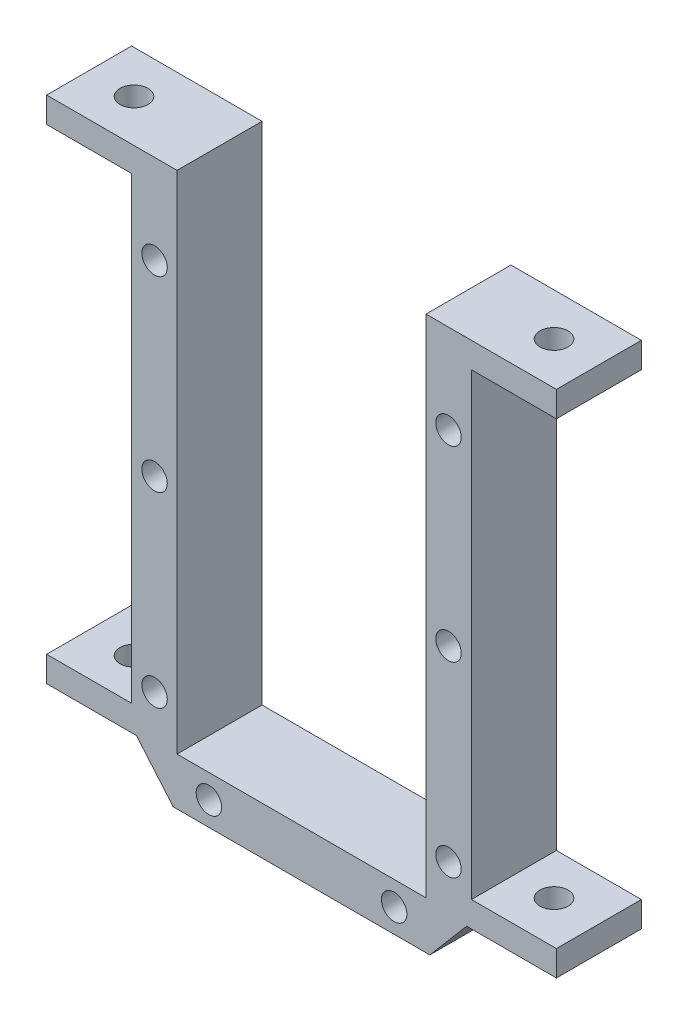
SolidWorks part; units mm, degrees
material "AISI 1035 Acier (SS)"
ref_plane "Front Plane" through (0, 0, 0) normal (0, 0, 1) x (1, 0, 0)
ref_plane "Top Plane" through (0, 0, 0) normal (0, 1, 0) x (1, 0, 0)
ref_plane "Right Plane" through (0, 0, 0) normal (1, 0, 0) x (0, 0, -1)
sketch "Sketch1" plane through (0, 0, 0) normal (0, 0, 1) x (1, 0, 0)
  line L1 (-20.1, 32.55) -> (19.9, 32.55)
  line L2 (-20.1, 32.55) -> (-20.1, -32.55)
  line L3 (-20.1, -32.55) -> (19.9, -32.55)
  line L4 (19.9, 32.55) -> (19.9, -32.55)
  point P0 (0, 0)
  dimension "D1" = 40
  dimension "D2" = 65.1
extrude "Boss-Extrude1" add sketch "Sketch1" along normal blind 10
sketch "Sketch2" plane through (0, 0, 10) normal (0, 0, 1) x (1, 0, 0)
  line L0 (-0.1, 32.55) -> (-0.1, -32.55) construction
  line L1 (19.9, 32.55) -> (-20.1, 32.55) construction
  line L2 (-20.1, -32.55) -> (19.9, -32.55) construction
  line L3 (-20.1, 0) -> (19.9, 0) construction
  line L4 (-20.1, 32.55) -> (-20.1, -32.55) construction
  line L5 (19.9, -32.55) -> (19.9, 32.55) construction
  line L6 (-20.1, -27.45) -> (19.9, -27.45) construction
  line L7 (15, -32.55) -> (19.335, -27.45)
  line L8 (19.335, -27.45) -> (15, -32.55) construction
  line L9 (19.335, -27.45) -> (19.9, -27.45)
  line L22 (19.9, -27.45) -> (19.9, -32.55)
  line L23 (19.9, -32.55) -> (15, -32.55)
  line L24 (-20.1, -27.45) -> (-20.1, -32.55)
  line L25 (-19.535, -27.45) -> (-20.1, -27.45)
  line L26 (-15.2, -32.55) -> (-19.535, -27.45)
  line L27 (-20.1, -32.55) -> (-15.2, -32.55)
  point P12 (-0.1, -27.45)
  point P13 (-19.535, -27.45)
  point P17 (-0.1, -27.45)
  point P18 (19.335, -27.45)
  dimension "D1" = 60
extrude "Cut-Extrude1" cut sketch "Sketch2" against normal blind 10
sketch "Sketch4" plane through (0, 0, 10) normal (0, 0, 1) x (1, 0, 0)
  line L0 (-0.1, 32.55) -> (-0.1, -32.55) construction
  line L1 (19.9, 32.55) -> (-20.1, 32.55) construction
  line L2 (-15.2, -32.55) -> (15, -32.55) construction
  line L3 (-20.1, 2.55) -> (19.9, 2.55) construction
  line L4 (-20.1, 32.55) -> (-20.1, -27.45) construction
  line L5 (19.9, -27.45) -> (19.9, 32.55) construction
  line L6 (14.55, -26.95) -> (-14.75, -26.95) construction
  line L7 (-14.75, -26.95) -> (-14.75, 32.55) construction
  line L8 (14.55, -26.95) -> (14.55, 32.55) construction
  line L9 (-14.75, 32.55) -> (-14.75, -26.95)
  line L10 (-14.75, -26.95) -> (14.55, -26.95)
  line L11 (14.55, -26.95) -> (14.55, 32.55)
  line L12 (14.55, 32.55) -> (-14.75, 32.55)
  point P12 (-0.1, -26.95)
  point P16 (-0.1, -26.95)
  dimension "D1" = 5.6
  dimension "D2" = 29.3
extrude "Cut-Extrude2" cut sketch "Sketch4" against normal blind 10
sketch "Sketch5" plane through (0, 0, 10) normal (0, 0, 1) x (1, 0, 0)
  line L0 (-14.75, 32.55) -> (14.55, 32.55) construction
  line L1 (-0.1, 32.55) -> (-0.1, -32.55) construction
  line L2 (-15.2, -32.55) -> (15, -32.55) construction
  line L3 (-15.2, -32.55) -> (15, -32.55) construction
  line L6 (-20.1, 32.55) -> (-20.1, -27.45) construction
  circle A0 centre (-17.4, 22.05) radius 1.5
  circle A1 centre (-17.4, 0.05) radius 1.5
  circle A2 centre (-17.4, -21.95) radius 1.5
  circle A3 centre (-11, -29.75) radius 1.5
  circle A4 centre (10.8, -29.75) radius 1.5
  circle A5 centre (17.2, -21.95) radius 1.5
  circle A6 centre (17.2, 0.05) radius 1.5
  circle A7 centre (17.2, 22.05) radius 1.5
  point P8 (-17.4, 22.05)
  point P9 (-17.4, 0.05)
  point P10 (-17.4, -21.95)
  point P11 (-11, -29.75)
  point P22 (10.8, -29.75)
  point P25 (17.2, -21.95)
  point P28 (17.2, 0.05)
  point P31 (17.2, 22.05)
  dimension "D6" = 3
  dimension "D7" = 3
  dimension "D8" = 3
  dimension "D9" = 3
  dimension "D1" = 10.6
  dimension "D2" = 32.6
  dimension "D3" = 54.6
  dimension "D4" = 2.8
  dimension "D5" = 9.1
  dimension "D10" = 17.3
  dimension "D11" = 17.3
  dimension "D12" = 17.3
extrude "Cut-Extrude3" cut sketch "Sketch5" against normal blind 10
sketch "Sketch6" plane through (0, 0, 10) normal (0, 0, 1) x (1, 0, 0)
  line L0 (-14.75, 32.55) -> (14.55, 32.55) construction
  line L1 (-0.1, 32.55) -> (-0.1, -32.55) construction
  line L2 (-15.2, -32.55) -> (15, -32.55) construction
  line L3 (-20.1, 2.55) -> (19.9, 2.55) construction
  line L4 (-20.1, 32.55) -> (-20.1, -27.45) construction
  line L5 (19.9, -27.45) -> (19.9, 32.55) construction
sketch "Sketch7" plane through (19.9, 0, 0) normal (1, 0, 0) x (0, 0, -1)
  line L0 (0, 2.55) -> (-10, 2.55) construction
  line L1 (-10, 32.55) -> (-10, -32.55) construction
  line L2 (0, -27.45) -> (0, 32.55) construction
  line L3 (0, 29.55) -> (-10, 29.55)
  line L4 (-10, 29.55) -> (-10, 32.55)
  line L5 (-10, 32.55) -> (0, 32.55)
  line L6 (0, 32.55) -> (0, 29.55)
  line L7 (-10, -27.45) -> (-10, 32.55) construction
  line L8 (-10, -27.45) -> (0, -27.45)
  line L9 (-10, -24.45) -> (-10, -27.45)
  line L10 (0, -24.45) -> (-10, -24.45)
  line L11 (0, -27.45) -> (0, -24.45)
  point P5 (0, 29.55)
  dimension "D1" = 3
extrude "Boss-Extrude2" add sketch "Sketch7" along normal blind 10
sketch "Sketch8" plane through (-20.1, 0, 0) normal (-1, 0, 0) x (0, 0, 1)
  line L0 (0, 2.55) -> (10, 2.55) construction
  line L1 (0, 32.55) -> (0, -27.45) construction
  line L2 (10, 32.55) -> (10, -32.55) construction
  line L3 (0, 29.55) -> (10, 29.55)
  line L4 (10, 29.55) -> (10, 32.55)
  line L5 (10, 32.55) -> (0, 32.55)
  line L6 (0, 32.55) -> (0, 29.55)
  line L7 (10, -27.45) -> (0, -27.45)
  line L8 (10, -24.45) -> (10, -27.45)
  line L9 (0, -24.45) -> (10, -24.45)
  line L10 (0, -27.45) -> (0, -24.45)
  point P6 (0, 29.55)
  dimension "D1" = 3
extrude "Boss-Extrude3" add sketch "Sketch8" along normal blind 10
sketch "Sketch9" plane through (0, -27.45, 0) normal (0, -1, 0) x (-1, 0, 0)
  line L0 (24.8175, -10) -> (24.8175, 0) construction
  line L1 (19.535, -10) -> (30.1, -10) construction
  line L2 (19.535, 0) -> (30.1, 0) construction
  line L3 (30.1, -5) -> (19.535, -5) construction
  line L4 (30.1, 0) -> (30.1, -10) construction
  line L5 (19.535, 0) -> (19.535, -10) construction
  circle A0 centre (24.8175, -5) radius 1.65
  dimension "D1" = 3.3
extrude "Cut-Extrude4" cut sketch "Sketch9" against normal through all
sketch "Sketch10" plane through (0, -27.45, 0) normal (0, -1, 0) x (-1, 0, 0)
  line L0 (-24.6175, -10) -> (-24.6175, 0) construction
  line L1 (-29.9, -10) -> (-19.335, -10) construction
  line L2 (-29.9, 0) -> (-19.335, 0) construction
  line L3 (-19.335, -5) -> (-29.9, -5) construction
  line L4 (-19.335, 0) -> (-19.335, -10) construction
  line L5 (-29.9, -10) -> (-29.9, 0) construction
  circle A0 centre (-24.6175, -5) radius 1.65
  dimension "D1" = 3.3
extrude "Cut-Extrude5" cut sketch "Sketch10" against normal through all
